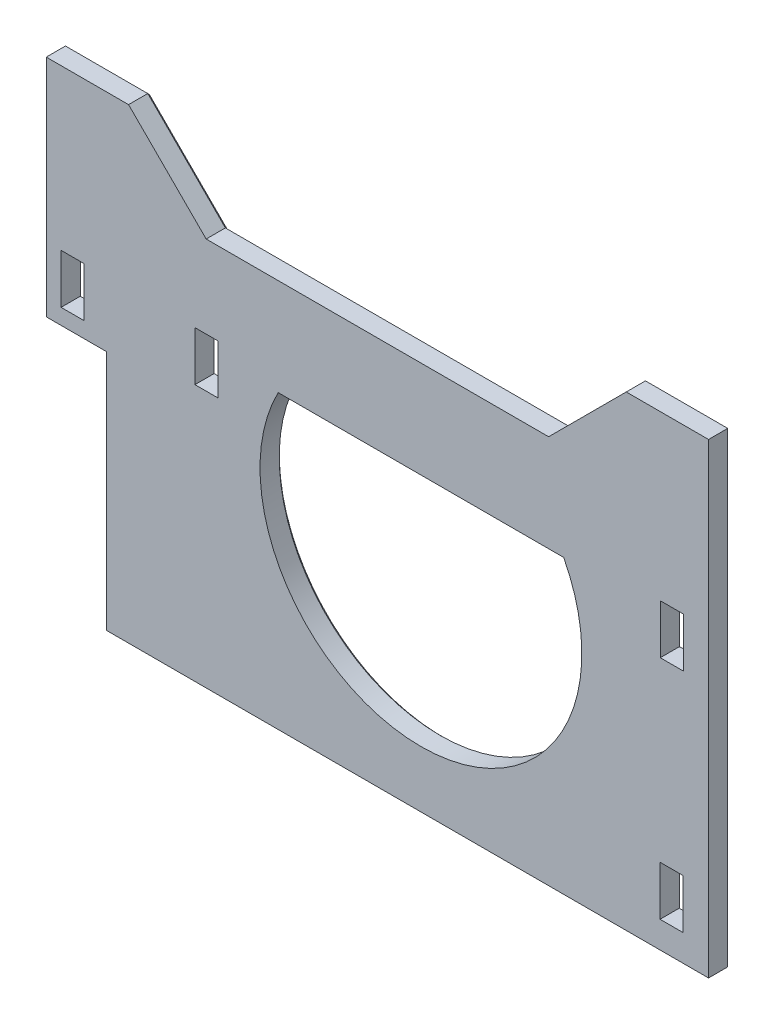
SolidWorks part; units mm, degrees
ref_plane "Front Plane" through (0, 0, 0) normal (0, 0, 1) x (1, 0, 0)
ref_plane "Top Plane" through (0, 0, 0) normal (0, 1, 0) x (1, 0, 0)
ref_plane "Right Plane" through (0, 0, 0) normal (1, 0, 0) x (0, 0, -1)
sketch "Sketch1" plane through (0, 0, 0) normal (0, 0, 1) x (1, 0, 0)
  line L0 (-25.9, 23.1791) -> (26.1356, 23.1791)
  line L6 (-41.0656, 25.85) -> (-36.8656, 25.85)
  line L9 (-41.0656, 25.85) -> (-41.0656, 16.85)
  line L12 (-41.0656, 16.85) -> (-36.8656, 16.85)
  line L15 (-36.8656, 25.85) -> (-36.8656, 16.85)
  line L51 (52.5344, 30) -> (52.5344, -30)
  line L54 (43.7344, 25.15) -> (47.9344, 25.15)
  line L55 (43.7344, 25.15) -> (43.7344, 16.15)
  line L56 (43.7344, 16.15) -> (47.9344, 16.15)
  line L57 (47.9344, 25.15) -> (47.9344, 16.15)
  line L58 (47.9, -16.15) -> (43.7, -16.15)
  line L59 (47.9, -16.15) -> (47.9, -25.15)
  line L60 (47.9, -25.15) -> (43.7, -25.15)
  line L61 (43.7, -16.15) -> (43.7, -25.15)
  line L65 (-65.4656, 25.85) -> (-61.2656, 25.85)
  line L66 (-65.4656, 25.85) -> (-65.4656, 16.85)
  line L67 (-65.4656, 16.85) -> (-61.2656, 16.85)
  line L68 (-61.2656, 25.85) -> (-61.2656, 16.85)
  line L76 (52.5344, 30) -> (-68.1656, 30)
  line L81 (-38.9656, 25.85) -> (-38.9656, 16.85) construction
  line L82 (-36.8656, 21.35) -> (-41.0656, 21.35) construction
  line L83 (-63.3656, 25.85) -> (-63.3656, 16.85) construction
  line L84 (-61.2656, 21.35) -> (-65.4656, 21.35) construction
  line L85 (47.9344, 20.65) -> (43.7344, 20.65) construction
  line L86 (45.8344, 25.15) -> (45.8344, 16.15) construction
  line L87 (45.8, -16.15) -> (45.8, -25.15) construction
  line L88 (47.9, -20.65) -> (43.7, -20.65) construction
  line L89 (-57.1656, -30) -> (-57.1656, 14)
  line L90 (-57.1656, 14) -> (-68.1656, 14)
  line L91 (-68.1656, 14) -> (-68.1656, 30)
  line L92 (-57.1656, -30) -> (52.5344, -30)
  arc A12 (-25.9, 23.1791) -> (26.1356, 23.1791) centre (0.1178, 9.6488) ccw
  point P0 (0.0344, 0)
  point P14 (52.5344, 0)
  point P25 (-7.8156, 30)
  dimension "D3" = 4.2
  dimension "D4" = 9
  dimension "D6" = 60
  dimension "D5" = 24.4
  dimension "D7" = 53.65
  dimension "D2" = 31.15
  dimension "D10" = 20.65
  dimension "D11" = 20.65
  dimension "D8" = 120.7
  dimension "D9" = 11
  dimension "D12" = 44
extrude "Boss-Extrude1" add sketch "Sketch1" along normal blind 4
sketch "Sketch2" plane through (0, 0, 0) normal (0, 0, 1) x (1, 0, 0)
  line L0 (-68.1656, 30) -> (52.5344, 30)
  line L4 (23.3922, 40.8579) -> (-39.0235, 40.8579)
  line L5 (-39.0235, 40.8579) -> (-53.1656, 55)
  line L6 (-53.1656, 55) -> (-68.1656, 55)
  line L7 (-68.1656, 55) -> (-68.1656, 30)
  line L8 (23.3922, 40.8579) -> (37.5344, 55)
  line L9 (37.5344, 55) -> (52.5344, 55)
  line L10 (52.5344, 55) -> (52.5344, 30)
  line L12 (-68.1656, 30) -> (-68.1656, 14) construction
  dimension "D1" = 25
  dimension "D2" = 20
  dimension "D3" = 15
  dimension "D4" = 135
extrude "Boss-Extrude2" add sketch "Sketch2" along normal blind 4
sketch "Sketch3" plane through (0, 0, 0) normal (0, 0, -1) x (-1, 0, 0)
  line L0 (-45.8344, 25.15) -> (-45.8344, 16.15) construction
  line L1 (-47.9344, 25.15) -> (-43.7344, 25.15) construction
  line L2 (-43.7344, 16.15) -> (-47.9344, 16.15) construction
  line L3 (-47.9344, 20.65) -> (-43.7344, 20.65) construction
  line L4 (-47.9344, 16.15) -> (-47.9344, 25.15) construction
  line L5 (-43.7344, 25.15) -> (-43.7344, 16.15) construction
  line L6 (-45.8, -16.15) -> (-45.8, -25.15) construction
  line L7 (-47.9, -16.15) -> (-43.7, -16.15) construction
  line L8 (-43.7, -25.15) -> (-47.9, -25.15) construction
  line L9 (-47.9, -20.65) -> (-43.7, -20.65) construction
  line L10 (-47.9, -25.15) -> (-47.9, -16.15) construction
  line L11 (-43.7, -16.15) -> (-43.7, -25.15) construction
  line L12 (38.9656, 25.85) -> (38.9656, 16.85) construction
  line L13 (36.8656, 25.85) -> (41.0656, 25.85) construction
  line L14 (41.0656, 16.85) -> (36.8656, 16.85) construction
  line L15 (36.8656, 21.35) -> (41.0656, 21.35) construction
  line L16 (36.8656, 16.85) -> (36.8656, 25.85) construction
  line L17 (41.0656, 25.85) -> (41.0656, 16.85) construction
  line L18 (63.3656, 25.85) -> (63.3656, 16.85) construction
  line L19 (61.2656, 25.85) -> (65.4656, 25.85) construction
  line L20 (65.4656, 16.85) -> (61.2656, 16.85) construction
  line L21 (61.2656, 21.35) -> (65.4656, 21.35) construction
  line L22 (61.2656, 16.85) -> (61.2656, 25.85) construction
  line L23 (65.4656, 25.85) -> (65.4656, 16.85) construction
chamfer "Chamfer1" distance 0.5 angle 45 28 edges at (45.8, -25.15, 0) (43.7, -20.65, 0) (45.8, -16.15, 0) (47.9, -20.65, 0) (-63.3656, 25.85, 0) (-61.2656, 21.35, 0) (-63.3656, 16.85, 0) (-65.4656, 21.35, 0) (0.1178, 23.1791, 0) (0.1178, -19.6769, 0) (-62.6656, 14, 0) (-57.1656, -8, 0) (-2.3156, -30, 0) (52.5344, 12.5, 0) (45.0344, 55, 0) (30.4633, 47.9289, 0) (-7.8156, 40.8579, 0) (-46.0946, 47.9289, 0) (-60.6656, 55, 0) (-68.1656, 34.5, 0) (-38.9656, 25.85, 0) (-36.8656, 21.35, 0) (-38.9656, 16.85, 0) (-41.0656, 21.35, 0) (45.8344, 25.15, 0) (47.9344, 20.65, 0) (45.8344, 16.15, 0) (43.7344, 20.65, 0)
equation "\"pin_hole_width\"=4.2"
equation "\"D3@Sketch1\"=\"pin_hole_width\""
equation "\"pin_hole_height\"=9"
equation "\"D4@Sketch1\"=\"pin_hole_height\""
